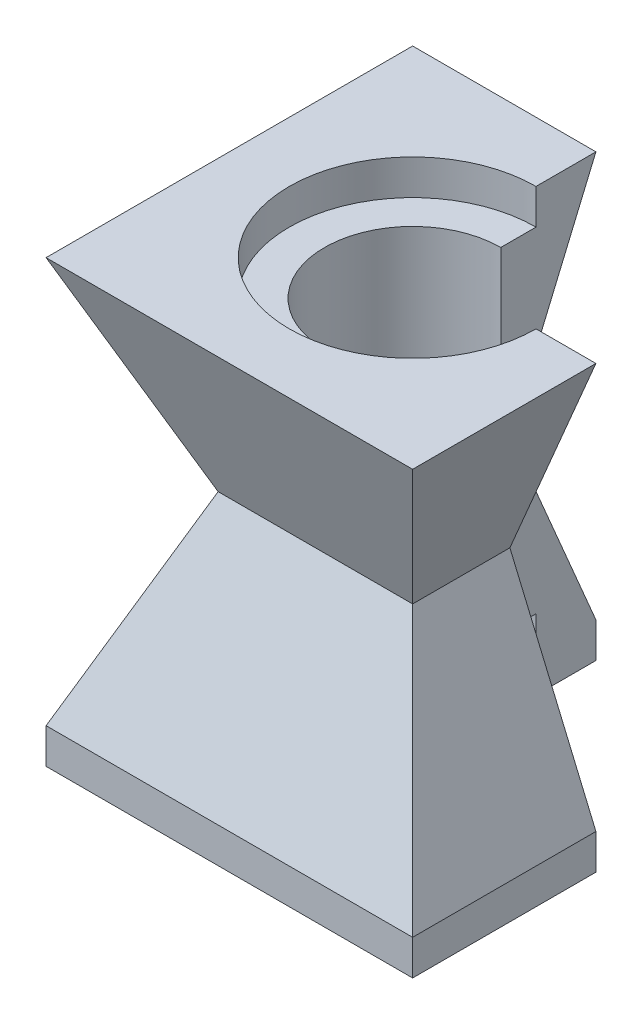
SolidWorks part; units mm, degrees
material "Cast Stainless Steel"
ref_plane "Front Plane" through (0, 0, 0) normal (0, 0, 1) x (1, 0, 0)
ref_plane "Top Plane" through (0, 0, 0) normal (0, 1, 0) x (1, 0, 0)
ref_plane "Right Plane" through (0, 0, 0) normal (1, 0, 0) x (0, 0, -1)
sketch "Sketch1" plane through (0, 0, 0) normal (0, 1, 0) x (1, 0, 0)
  line L1 (-52, -52) -> (52, -52)
  line L2 (-52, -52) -> (-52, 52)
  line L3 (-52, 52) -> (52, 52)
  line L4 (52, -52) -> (52, 52)
  line L5 (-52, -52) -> (52, 52) construction
  line L6 (-52, 52) -> (52, -52) construction
  circle A0 centre (0, 0) radius 25
  point P0 (0, 0)
  dimension "D2" = 50
  dimension "D1" = 104
extrude "Boss-Extrude1" add sketch "Sketch1" along normal blind 57.5 draft 23 contours A0 | L1 L4 L3 L2 A0 region at (-50.5292, 0, 0) region at (0, 0, 0)
mirror "Mirror1" about plane through (0, 57.5, 0) normal (0, 1, 0) of "Boss-Extrude1"
extrude "Cut-Extrude1" cut sketch "Sketch1<3>" along normal through all contours A0 region at (0, 0, 0)
sketch "Sketch1<3>" plane through (0, 0, 0) normal (0, 1, 0) x (1, 0, 0) same geometry as "Sketch1"
sketch "Sketch2" plane through (0, 0, 0) normal (0, -1, 0) x (1, 0, 0)
  line L0 (0, 0) -> (0, -52)
  line L1 (-52, -52) -> (52, -52) construction
  line L2 (0, 0) -> (52, 0)
  line L3 (52, 52) -> (52, -52) construction
  arc A0 (35, 0) -> (0, -35) centre (0, 0) ccw
  circle M2 centre (0, 0) radius 25
  line M5 (-52, -52) -> (52, -52)
  line M6 (52, -52) -> (52, 52)
  dimension "D1" = 35
extrude "Cut-Extrude2" cut sketch "Sketch2" against normal blind 10 contours L2 A0 L0 M2 region at (-0.9899, 0, -30)
extrude "Cut-Extrude3" cut sketch "Sketch2<3>" against normal through all contours L2 L0 M2 M5 M6 region at (29.4134, 0, -29.4134)
sketch "Sketch2<3>" plane through (0, 0, 0) normal (0, -1, 0) x (1, 0, 0) same geometry as "Sketch2"
ref_plane "Plane1" through (0, 57.5, 0) normal (0, -1, 0) x (-1, 0, 0)
mirror "Mirror2" about plane through (0, 57.5, 0) normal (0, -1, 0) of "Cut-Extrude2"
sketch "Sketch3" plane through (0, 0, 0) normal (0, -1, 0) x (1, 0, 0)
  line L0 (0, 0) -> (49, 49) construction
  line L1 (40.6586, 40.6586) -> (30.052, 30.052) construction
  line L2 (42.78, 38.5373) -> (32.1734, 27.9307)
  line L3 (38.5373, 42.78) -> (27.9307, 32.1734)
  line L4 (0, 0) -> (49, -49) construction
  line L5 (40.6586, -40.6586) -> (30.052, -30.052) construction
  line L6 (38.5373, -42.78) -> (27.9307, -32.1734)
  line L7 (42.78, -38.5373) -> (32.1734, -27.9307)
  line L8 (0, 0) -> (-49, -49) construction
  line L9 (-40.6586, -40.6586) -> (-30.052, -30.052) construction
  line L10 (-42.78, -38.5373) -> (-32.1734, -27.9307)
  line L11 (-38.5373, -42.78) -> (-27.9307, -32.1734)
  line L21 (0, -35) -> (-3, -35)
  line L22 (0, -35) -> (0, -52) construction
  line L23 (35, 3) -> (35, 0)
  line L24 (0, 0) -> (-49, 49) construction
  line L25 (-40.6586, 40.6586) -> (-30.052, 30.052) construction
  line L26 (-38.5373, 42.78) -> (-27.9307, 32.1734)
  line L27 (49, 49) -> (49, 3)
  line L28 (49, 3) -> (35, 3)
  line L29 (-3, -35) -> (-3, -49)
  line L30 (-3, -49) -> (-49, -49)
  line L31 (-49, 49) -> (49, 49)
  line L32 (-49, -49) -> (-49, 49)
  line L33 (49, 49) -> (49, 3)
  line L34 (49, 3) -> (35, 3)
  line L35 (-3, -35) -> (-3, -49)
  line L36 (-3, -49) -> (-49, -49)
  line L37 (-49, 49) -> (49, 49)
  line L38 (-49, -49) -> (-49, 49)
  line L39 (-42.78, 38.5373) -> (-32.1734, 27.9307)
  arc A0 (35, 0) -> (0, -35) centre (0, 0) ccw construction
  arc A1 (-38.5373, 42.78) -> (-42.78, 38.5373) centre (-40.6586, 40.6586) ccw
  arc A2 (-32.1734, 27.9307) -> (-27.9307, 32.1734) centre (-30.052, 30.052) ccw
  arc A3 (42.78, 38.5373) -> (38.5373, 42.78) centre (40.6586, 40.6586) ccw
  arc A4 (27.9307, 32.1734) -> (32.1734, 27.9307) centre (30.052, 30.052) ccw
  arc A5 (38.5373, -42.78) -> (42.78, -38.5373) centre (40.6586, -40.6586) ccw
  arc A6 (32.1734, -27.9307) -> (27.9307, -32.1734) centre (30.052, -30.052) ccw
  arc A7 (-42.78, -38.5373) -> (-38.5373, -42.78) centre (-40.6586, -40.6586) ccw
  arc A8 (-27.9307, -32.1734) -> (-32.1734, -27.9307) centre (-30.052, -30.052) ccw
  point P10 (-35.3553, 35.3553)
  point P15 (0, 0)
  point P20 (35.3553, 35.3553)
  point P28 (35.3553, -35.3553)
  point P45 (-35.3553, -35.3553)
  line M11 (35, 0) -> (52, 0)
  line M12 (52, 0) -> (52, 52)
  line M13 (52, 52) -> (-52, 52)
  line M14 (-52, 52) -> (-52, -52)
  line M15 (-52, -52) -> (0, -52)
  line M16 (0, -52) -> (0, -35)
  dimension "D4" = 3
  dimension "D2" = 50
  dimension "D3" = 15
  dimension "D1" = 3
  dimension "D5" = 4
extrude "Cut-Extrude4" cut sketch "Sketch3" against normal blind 10 contours L39 A2 L26 A1 | L11 A8 L10 A7 | L3 A4 L2 A3 region at (35.3553, 0, 35.3553) region at (-35.3553, 0, -35.3553) region at (-35.3553, 0, 35.3553)
extrude "Boss-Extrude2" add sketch "Sketch3<3>" along normal blind 10 contours L36 L38 L37 L33 L34 L23 L21 L35 M11 M12 M13 M14 M15 M16 region at (-1.4708, 0, -43.5)
sketch "Sketch3<3>" plane through (0, 0, 0) normal (0, -1, 0) x (1, 0, 0) same geometry as "Sketch3"
